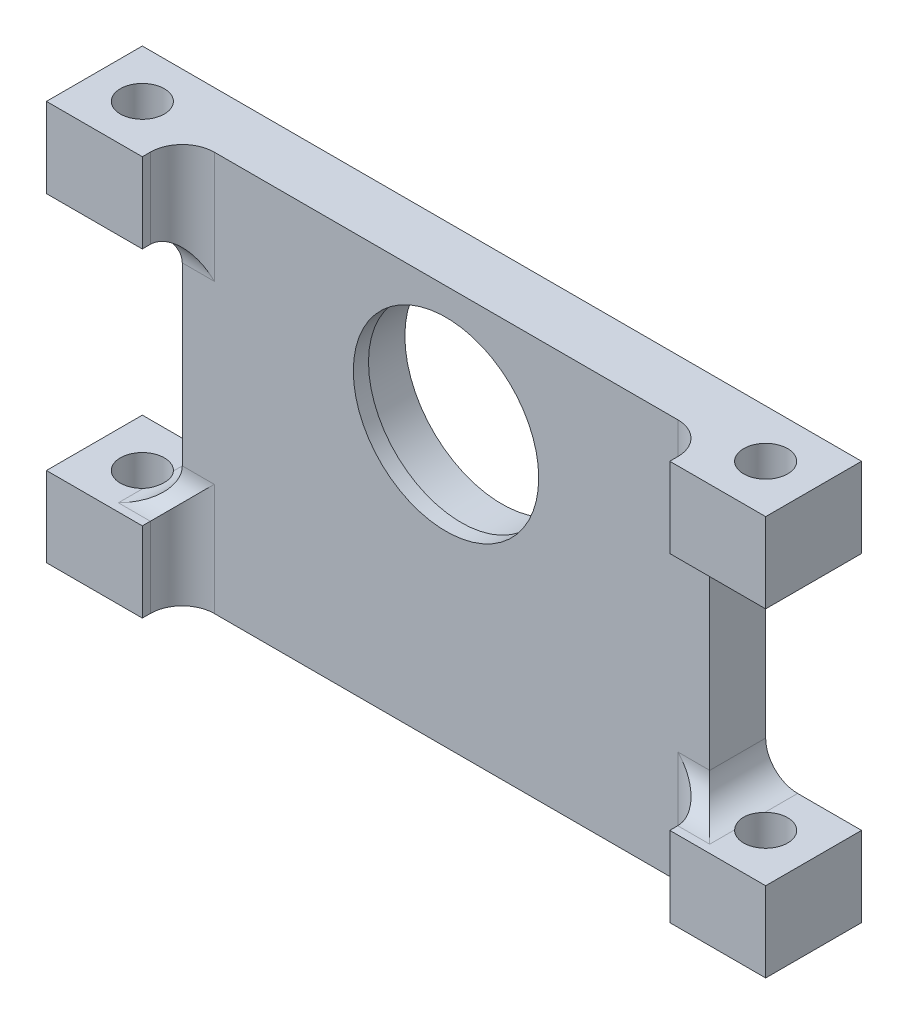
SolidWorks part; units mm, degrees
ref_plane "Front Plane" through (0, 0, 0) normal (0, 0, 1) x (1, 0, 0)
ref_plane "Top Plane" through (0, 0, 0) normal (0, 1, 0) x (1, 0, 0)
ref_plane "Right Plane" through (0, 0, 0) normal (1, 0, 0) x (0, 0, -1)
sketch "Sketch1" plane through (0, 0, 0) normal (0, 0, 1) x (1, 0, 0)
  line L1 (45, 50) -> (78, 50)
  line L2 (45, 50) -> (45, 46.6)
  line L3 (45, 0) -> (78, 0)
  line L4 (78, 50) -> (78, 0)
  line L7 (45, 23.4) -> (45, 0)
  arc A0 (45, 23.4) -> (45, 46.6) centre (45, 35) ccw
  dimension "D3" = 11.6
  dimension "D1" = 50
  dimension "D2" = 33
  dimension "D4" = 15
extrude "Boss-Extrude1" add sketch "Sketch1" along normal blind 7 separate body
sketch "Sketch2" plane through (0, 0, 0) normal (0, 0, -1) x (-1, 0, 0)
  line L0 (-78, 0) -> (-78, 50) construction
  line L1 (-90, 50) -> (-78, 50)
  line L2 (-90, 50) -> (-90, 40)
  line L3 (-90, 40) -> (-78, 40)
  line L4 (-78, 50) -> (-78, 40)
  line L5 (-78, 0) -> (-78, 10)
  line L6 (-78, 25) -> (-102.6679, 25) construction
  line L7 (-90, 10) -> (-78, 10)
  line L8 (-90, 0) -> (-90, 10)
  line L9 (-90, 0) -> (-78, 0)
  dimension "D1" = 10
  dimension "D2" = 12
extrude "Boss-Extrude2" add sketch "Sketch2" against normal blind 12
fillet "Fillet1" radius 4 2 edges at (78, 10, 3.5) (78, 40, 3.5)
fillet "Fillet2" radius 4 4 edges at (78, 5, 7) (80, 10, 7) (78, 45, 7) (80, 40, 7)
sketch "Sketch3" plane through (0, 50, 0) normal (0, 1, 0) x (1, 0, 0)
  line L0 (78, -12) -> (78, 0) construction
  line L1 (90, 0) -> (45, 0) construction
  line L2 (78, -6) -> (90, -6) construction
  line L3 (90, -12) -> (90, 0) construction
  line L4 (84, -12) -> (84, 0) construction
  line L5 (78, -12) -> (90, -12) construction
  circle A0 centre (84, -6) radius 2.75
  dimension "D1" = 5.5
extrude "Cut-Extrude1" cut sketch "Sketch3" against normal through all
sketch "Sketch4" plane through (0, 0, 0) normal (0, 0, -1) x (-1, 0, 0)
  circle A0 centre (-45, 35) radius 12.15
  dimension "D1" = 24.3
extrude "Cut-Extrude2" cut sketch "Sketch4" against normal blind 5.1
mirror "Mirror1" about plane through (45, 23.4, 7) normal (1, 0, 0) of bodies 105
